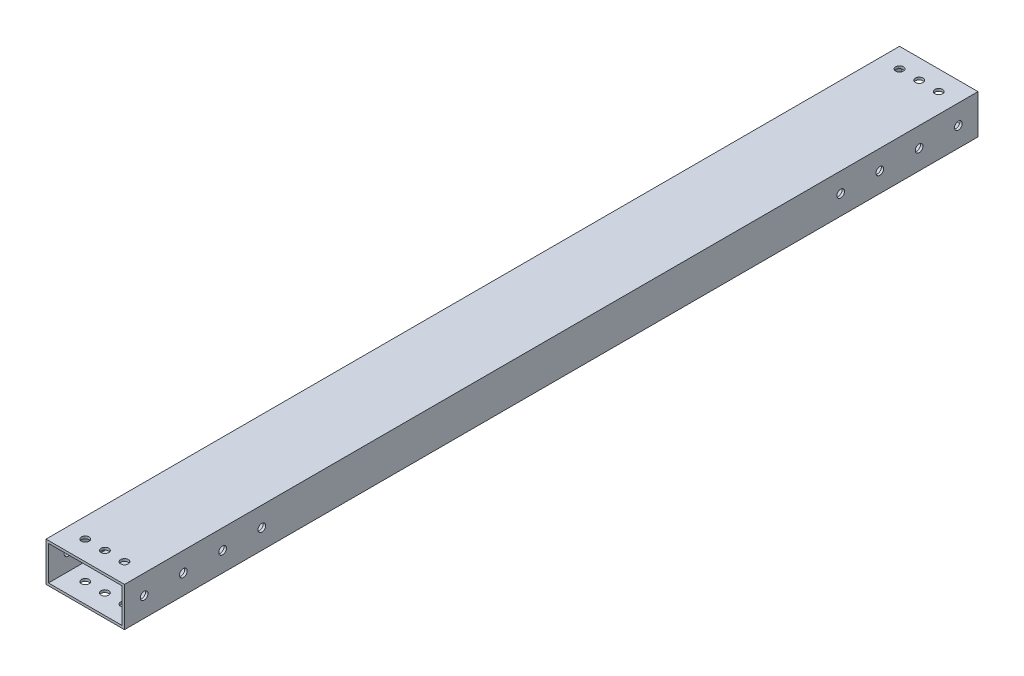
SolidWorks part; units mm, degrees
material "6061-T6 (SS)"
ref_plane "Front Plane" through (0, 0, 0) normal (0, 0, 1) x (1, 0, 0)
ref_plane "Top Plane" through (0, 0, 0) normal (0, 1, 0) x (1, 0, 0)
ref_plane "Right Plane" through (0, 0, 0) normal (1, 0, 0) x (0, 0, -1)
sketch "Sketch1" plane through (0, 0, 0) normal (0, 0, 1) x (1, 0, 0)
  line L0 (-23.8125, 11.1125) -> (23.8125, 11.1125)
  line L1 (-25.4, -12.7) -> (25.4, -12.7)
  line L2 (-25.4, -12.7) -> (-25.4, 12.7)
  line L3 (-25.4, 12.7) -> (25.4, 12.7)
  line L4 (25.4, -12.7) -> (25.4, 12.7)
  line L5 (-25.4, -12.7) -> (25.4, 12.7) construction
  line L6 (-25.4, 12.7) -> (25.4, -12.7) construction
  line L7 (23.8125, -11.1125) -> (23.8125, 11.1125)
  line L8 (-23.8125, -11.1125) -> (23.8125, -11.1125)
  line L9 (-23.8125, -11.1125) -> (-23.8125, 11.1125)
  point P0 (0, 0)
  dimension "D1" = 50.8
  dimension "D2" = 25.4
  dimension "D3" = 1.5875
extrude "Boss-Extrude1" add sketch "Sketch1" along normal mid plane 552.45
sketch "Sketch2" plane through (0, 12.7, 0) normal (0, 1, 0) x (1, 0, 0)
  line L0 (25.4, 276.225) -> (-25.4, 276.225) construction
  line L1 (-25.4, 0) -> (25.4, 0) construction
  line L2 (-25.4, -276.225) -> (-25.4, 276.225) construction
  line L3 (25.4, -276.225) -> (25.4, 276.225) construction
  circle A0 centre (-12.7, 263.525) radius 2.4892
  circle A1 centre (0, 263.525) radius 2.4892
  circle A2 centre (12.7, 263.525) radius 2.4892
  circle A3 centre (12.7, -263.525) radius 2.4892
  circle A4 centre (0, -263.525) radius 2.4892
  circle A5 centre (-12.7, -263.525) radius 2.4892
  point P9 (0, 276.225)
  dimension "D1" = 4.9784
  dimension "D2" = 12.7
  dimension "D3" = 12.7
  dimension "D4" = 12.7
extrude "Cut-Extrude1" cut sketch "Sketch2" against normal through all
sketch "Sketch3" plane through (25.4, 0, 0) normal (1, 0, 0) x (0, 0, -1)
  line L0 (276.225, -12.7) -> (276.225, 12.7) construction
  line L1 (0, 12.7) -> (0, -12.7) construction
  line L2 (-276.225, 12.7) -> (276.225, 12.7) construction
  line L3 (-276.225, -12.7) -> (276.225, -12.7) construction
  circle A0 centre (263.525, 0) radius 2.4892
  circle A1 centre (-263.525, 0) radius 2.4892
  circle A2 centre (238.125, 0) radius 2.4892
  circle A3 centre (212.725, 0) radius 2.4892
  circle A4 centre (187.325, 0) radius 2.4892
  circle A7 centre (-187.325, 0) radius 2.4892
  circle A8 centre (-212.725, 0) radius 2.4892
  circle A9 centre (-238.125, 0) radius 2.4892
  point P5 (276.225, 0)
  dimension "D1" = 12.7
  dimension "D2" = 4.9784
  dimension "D4" = 25.4
  dimension "D3" = 4
extrude "Cut-Extrude2" cut sketch "Sketch3" against normal through all
